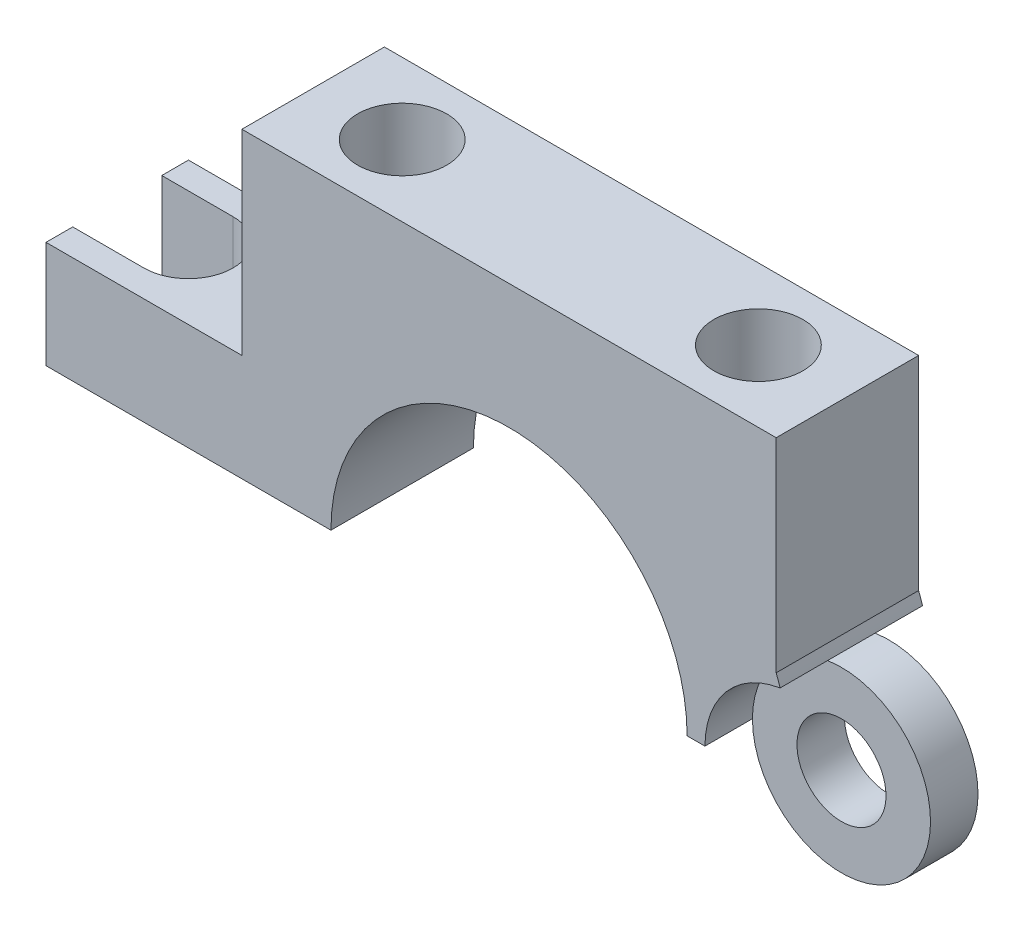
SolidWorks part; units mm, degrees
ref_plane "Front Plane" through (0, 0, 0) normal (0, 0, 1) x (1, 0, 0)
ref_plane "Top Plane" through (0, 0, 0) normal (0, 1, 0) x (1, 0, 0)
ref_plane "Right Plane" through (0, 0, 0) normal (1, 0, 0) x (0, 0, -1)
sketch "Sketch1" plane through (0, 0, 0) normal (0, 0, 1) x (1, 0, 0)
  line L0 (55, 0) -> (-55, 0) construction
  line L1 (-5, 0) -> (-13, 0)
  line L2 (-13, 0) -> (-13, 3)
  line L3 (-13, 3) -> (-7.4162, 3)
  line L4 (5, 0) -> (8, 0)
  arc A0 (-8, 0) -> (8, 0) centre (0, 0) cw
  arc A1 (-5, 0) -> (5, 0) centre (0, 0) cw
  dimension "D1" = 5
  dimension "D2" = 8
  dimension "D3" = 3
  dimension "D4" = 5
extrude "Boss-Extrude1" add sketch "Sketch1" along normal mid plane 4 contours L1 A1 L4 A0 | L1 A0 L3 L2 region at (-6.5, 0.1789, 0) region at (-10.4013, 1.5279, 0)
sketch "Sketch2" plane through (0, 0, 0) normal (0, 0, 1) x (1, 0, 0)
  line L0 (55, 0) -> (-55, 0) construction
  circle A0 centre (8, 0) radius 2.5
  arc A1 (8, 0) -> (-7.4162, 3) centre (0, 0) ccw construction
  dimension "D1" = 5
extrude "Boss-Extrude2" add sketch "Sketch2" along normal mid plane 1.3333
sketch "Sketch3" plane through (0, 0, 2) normal (0, 0, 1) x (1, 0, 0)
  line L0 (55, 0) -> (-55, 0) construction
  circle A0 centre (8, 0) radius 1.25
  arc A1 (5.5, 0) -> (7.6094, 2.4693) centre (8, 0) ccw construction
  dimension "D1" = 2.5
  dimension "D2" = 0
extrude "Cut-Extrude1" cut sketch "Sketch3" against normal up to surface (4 mm away) up to face at (-4.03, 2.8921, -2)
sketch "Sketch4" plane through (0, 3, 0) normal (0, 1, 0) x (1, 0, 0)
  line L0 (-44.2539, 0) -> (44.2539, 0) construction
  line L1 (-11, 1.25) -> (-13, 1.25)
  line L2 (-13, -2) -> (-13, 2) construction
  line L3 (-11, -1.25) -> (-13, -1.25)
  arc A0 (-11, 1.25) -> (-11, -1.25) centre (-11, 0) cw
  line M5 (-13, 2) -> (-13, -2)
  dimension "D1" = 1.25
  dimension "D2" = 2
extrude "Cut-Extrude3" cut sketch "Sketch4" against normal blind 3 and the other way through all contours A0 L1 L3 M5 region at (-11.4961, 3, 0)
sketch "Sketch6" plane through (0, 0, 0) normal (0, 0, 1) x (1, 0, 0)
  line L1 (-7.5, 8.5) -> (7.5, 8.5)
  line L2 (-7.5, 8.5) -> (-7.5, 2.7839)
  line L4 (7.5, 8.5) -> (7.5, 2.7839)
  line L5 (0, -44.7868) -> (0, 44.7868) construction
  line L6 (55, 0) -> (-55, 0) construction
  arc A0 (7.9023, 1.2462) -> (-7.4162, 3) centre (0, 0) ccw construction
  arc A1 (-7.5, 2.7839) -> (7.5039, 2.7734) centre (0, 0) cw
  dimension "D1" = 15
  dimension "D2" = 7.5
  dimension "D3" = 8.5
extrude "Boss-Extrude3" add sketch "Sketch6" along normal mid plane 4 contours L2 A1 L4 L1 region at (0, 8.3395, 0)
sketch "Sketch7" plane through (0, 0, 0) normal (0, 0, 1) x (1, 0, 0)
  circle A0 centre (8, 0) radius 2.5
  dimension "D1" = 5
extrude "Cut-Extrude8" cut sketch "Sketch7" against normal up to surface (2 mm away) from surface up to face at (-1.1553, 3.2266, -2) starting at face at (8.1809, -0.1522, -0.6667)
sketch "Sketch8" plane through (0, 0, 0) normal (0, 0, 1) x (1, 0, 0)
  circle A0 centre (8, 0) radius 2.5
  dimension "D1" = 5
extrude "Cut-Extrude9" cut sketch "Sketch8" along normal up to surface (2 mm away) from surface up to face at (-1.1553, 3.2266, 2) starting at face at (8.1809, -0.1522, 0.6667)
sketch "Sketch9" plane through (0, 8.5, 0) normal (0, 1, 0) x (1, 0, 0)
  line L0 (-44.2539, 0) -> (44.2539, 0) construction
  line L1 (0, -44.7868) -> (0, 44.7868) construction
  circle A0 centre (-5, 0) radius 1.25
  circle A1 centre (5, 0) radius 1.25
  point P8 (6.0591, -6.4348)
  dimension "D1" = 10
  dimension "D2" = 2.5
  dimension "D3" = 5
extrude "Cut-Extrude10" cut sketch "Sketch9" against normal blind 5
equation "\"InnerRad\"= 5"
equation "\"D1@Sketch1\"=\"InnerRad\""
equation "\"D2@Sketch1\"=\"InnerRad\"+3"
equation "\"ScPlLength\"=20"
equation "\"ScPlThickness\"=3"
equation "\"D3@Sketch6\"=\"InnerRad\"+3.5"
equation "\"D1@Boss-Extrude3\"=4"
